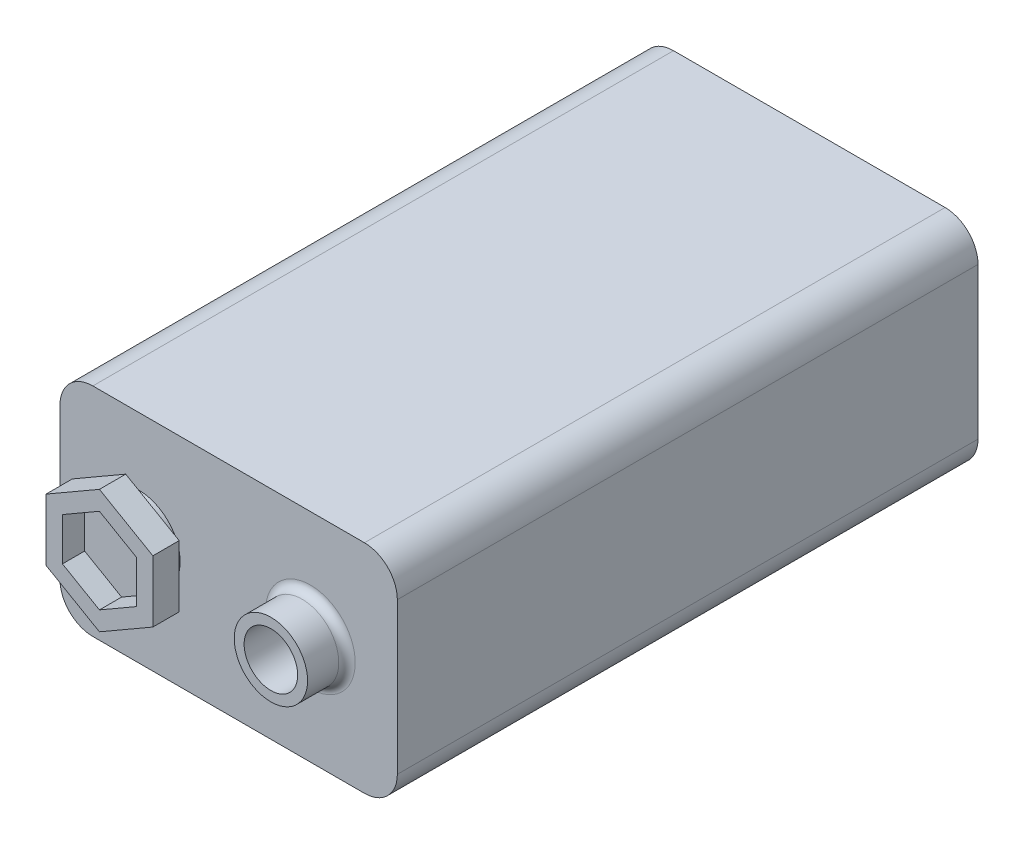
SolidWorks part; units mm, degrees
ref_plane "Front Plane" through (0, 0, 0) normal (0, 0, 1) x (1, 0, 0)
ref_plane "Top Plane" through (0, 0, 0) normal (0, 1, 0) x (1, 0, 0)
ref_plane "Right Plane" through (0, 0, 0) normal (1, 0, 0) x (0, 0, -1)
ref_axis "Axis1" through (-88.99, 0, 0) along (1, 0, 0)
ref_axis "Axis2" through (0, 55, 0) along (0, -1, 0)
ref_axis "Axis3" through (0, 0, 55) along (0, 0, -1)
ref_point "Point1"
sketch "Sketch1" plane through (0, 0, 0) normal (0, 1, 0) x (1, 0, 0)
  line L1 (-13.0302, -22.4282) -> (13.0302, -22.4282)
  line L2 (-13.0302, -22.4282) -> (-13.0302, 22.4282)
  line L3 (-13.0302, 22.4282) -> (13.0302, 22.4282)
  line L4 (13.0302, -22.4282) -> (13.0302, 22.4282)
  line L5 (-13.0302, -22.4282) -> (13.0302, 22.4282) construction
  line L6 (-13.0302, 22.4282) -> (13.0302, -22.4282) construction
  point P0 (0, 0)
  dimension "D1" = 44.8564
  dimension "D2" = 26.0604
extrude "Boss-Extrude1" add sketch "Sketch1" along normal mid plane 16.764
sketch "Sketch2" plane through (0, 0, 22.4282) normal (0, 0, 1) x (1, 0, 0)
  line L0 (13.0302, 0) -> (9.144, 0) construction
  line L1 (13.0302, 8.382) -> (13.0302, -8.382) construction
  circle A0 centre (6.3119, 0) radius 2.8321
  circle A1 centre (6.3119, 0) radius 2.0701
  dimension "D2" = 5.6642
  dimension "D1" = 3.8862
  dimension "D3" = 0.762
extrude "Boss-Extrude2" add sketch "Sketch2" along normal blind 3.2258
sketch "Sketch3" plane through (0, 0, 22.4282) normal (0, 0, 1) x (1, 0, 0)
  line L0 (-13.0302, 8.382) -> (-13.0302, -8.382) construction
  circle A0 centre (-6.9342, 0) radius 3.1877
  dimension "D1" = 6.3754
  dimension "D2" = 6.096
extrude "Boss-Extrude3" add sketch "Sketch3" along normal blind 1.016
sketch "Sketch4" plane through (0, 0, 23.4442) normal (0, 0, 1) x (1, 0, 0)
  line L0 (-13.0302, 8.382) -> (-13.0302, -8.382) construction
  line L1 (-2.8067, 2.383) -> (-6.9342, 4.766)
  line L2 (-6.9342, 4.766) -> (-11.0617, 2.383)
  line L3 (-11.0617, 2.383) -> (-11.0617, -2.383)
  line L4 (-11.0617, -2.383) -> (-6.9342, -4.766)
  line L5 (-6.9342, -4.766) -> (-2.8067, -2.383)
  line L6 (-2.8067, -2.383) -> (-2.8067, 2.383)
  line L7 (-9.7917, 1.6498) -> (-9.7917, -1.6498)
  line L8 (-9.7917, -1.6498) -> (-6.9342, -3.2996)
  line L9 (-6.9342, -3.2996) -> (-4.0767, -1.6498)
  line L10 (-4.0767, -1.6498) -> (-4.0767, 1.6498)
  line L11 (-4.0767, 1.6498) -> (-6.9342, 3.2996)
  line L12 (-6.9342, 3.2996) -> (-9.7917, 1.6498)
  circle A0 centre (-6.9342, 0) radius 4.1275 construction
  dimension "D1" = 8.255
  dimension "D2" = 1.27
extrude "Boss-Extrude4" add sketch "Sketch4" along normal offset from surface (2.5654 mm away) 3.5814 up to face at (-10.1219, 0, 22.4282) offset beyond the face yes
fillet "Fillet1" radius 2.54 4 edges at (13.0302, 8.382, 0) (13.0302, -8.382, 0) (-13.0302, -8.382, 0) (-13.0302, 8.382, 0)
fillet "Fillet2" radius 0.635 1 edges at (3.4798, 0, 22.4282)
sketch "Sketch5" plane through (0, 0, 23.4442) normal (0, 0, 1) x (1, 0, 0)
  line L0 (-9.7917, -1.6498) -> (-9.7917, 1.6498) construction
  line L1 (-6.9342, -3.2996) -> (-9.7917, -1.6498) construction
  line L2 (-4.0767, -1.6498) -> (-6.9342, -3.2996) construction
  line L3 (-4.0767, 1.6498) -> (-4.0767, -1.6498) construction
  line L4 (-9.7917, 1.6498) -> (-6.9342, 3.2996) construction
  line L5 (-6.9342, 3.2996) -> (-4.0767, 1.6498) construction
  line L6 (-9.7917, -1.6498) -> (-9.7917, 1.6498)
  line L7 (-6.9342, -3.2996) -> (-9.7917, -1.6498)
  line L8 (-4.0767, -1.6498) -> (-6.9342, -3.2996)
  line L9 (-4.0767, 1.6498) -> (-4.0767, -1.6498)
  line L10 (-9.7917, 1.6498) -> (-6.9342, 3.2996)
  line L11 (-6.9342, 3.2996) -> (-4.0767, 1.6498)
extrude "Boss-Extrude5" add sketch "Sketch5" along normal blind 0.3175
fillet "Fillet3" radius 0.635 1 edges at (-3.7465, 0, 23.4442)
sketch "Sketch6" plane through (0, 0, 26.0096) normal (0, 0, 1) x (1, 0, 0)
  line L1 (-13.7797, 13.7991) -> (13.7797, 13.7991)
  line L2 (-13.7797, 13.7991) -> (-13.7797, -13.7991)
  line L3 (-13.7797, -13.7991) -> (13.7797, -13.7991)
  line L4 (13.7797, 13.7991) -> (13.7797, -13.7991)
  line L5 (-13.7797, 13.7991) -> (13.7797, -13.7991) construction
  line L18 (-13.7797, -13.7991) -> (13.7797, 13.7991) construction
  point P0 (0, 0)
extrude "Cut-Extrude1" cut sketch "Sketch6" against normal offset from surface (0.5334 mm away) 47.9044 up to face at (0, 0, -22.4282)
